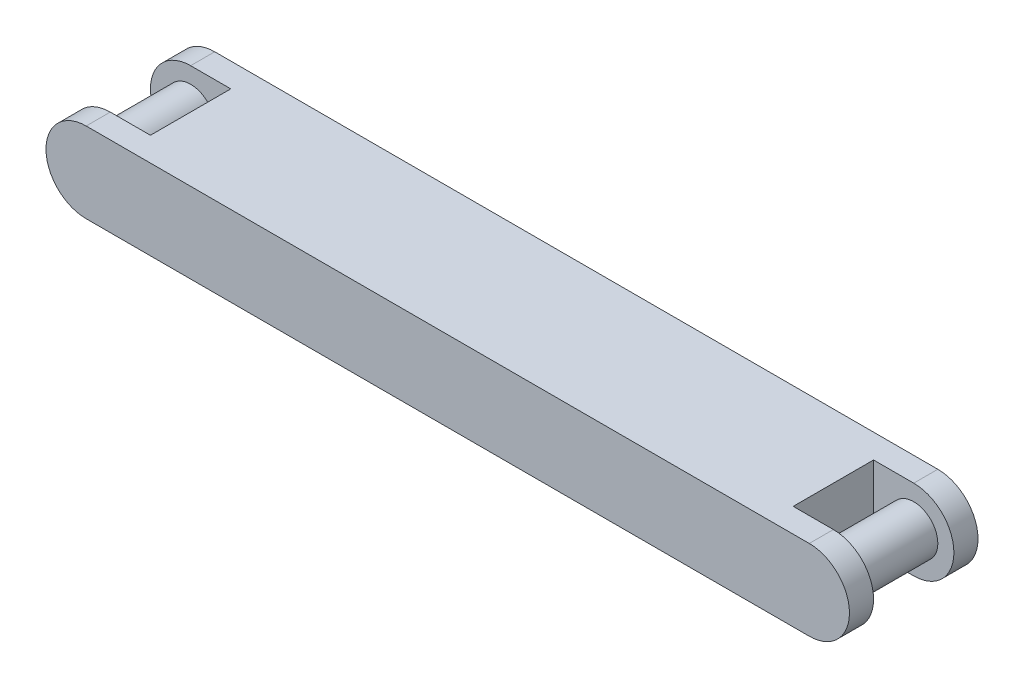
SolidWorks part; units mm, degrees
ref_plane "Front Plane" through (0, 0, 0) normal (0, 0, 1) x (1, 0, 0)
ref_plane "Top Plane" through (0, 0, 0) normal (0, 1, 0) x (1, 0, 0)
ref_plane "Right Plane" through (0, 0, 0) normal (1, 0, 0) x (0, 0, -1)
sketch "Sketch1" plane through (0, 0, 0) normal (0, 0, 1) x (1, 0, 0)
  line L0 (-142.875, 15.875) -> (-127, 15.875)
  line L1 (-127, -15.875) -> (127, -15.875)
  line L2 (-127, -15.875) -> (-127, 15.875)
  line L3 (-127, 15.875) -> (127, 15.875)
  line L4 (127, -15.875) -> (127, 15.875)
  line L5 (-127, -15.875) -> (127, 15.875) construction
  line L6 (-127, 15.875) -> (127, -15.875) construction
  line L7 (-142.875, -15.875) -> (-127, -15.875)
  line L8 (0, 15.875) -> (0, -15.875) construction
  line L9 (142.875, -15.875) -> (127, -15.875)
  line L10 (142.875, 15.875) -> (127, 15.875)
  circle A0 centre (-142.875, 0) radius 9.525
  circle A1 centre (-142.875, 0) radius 15.875
  circle A2 centre (142.875, 0) radius 9.525
  circle A3 centre (142.875, 0) radius 15.875
  point P0 (0, 0)
  dimension "D1" = 31.75
  dimension "D2" = 19.05
  dimension "D3" = 254
extrude "Boss-Extrude1" add sketch "Sketch1" along normal blind 25.4 and the other way blind 25.4 contours L1 L4 L3 L2 | A0 | A2 region at (0, 0, 0)
extrude "Boss-Extrude2" add sketch "Sketch1<4>" against normal blind 9.525 from surface contours A1 L2 L0 | A1 A0 | A1 L7 L2 | L4 A3 L10 | A3 A2 | L9 A3 L4 region at (-130.546, 12.329, 0) region at (-131.9672, 10.9078, 0) region at (-130.546, -12.329, 0) region at (130.546, 12.329, 0) region at (130.546, -12.329, 0) region at (131.9672, 10.9078, 0) starting at face at (0, 0, 25.4)
sketch "Sketch1<4>" plane through (0, 0, 0) normal (0, 0, 1) x (1, 0, 0) same geometry as "Sketch1"
extrude "Boss-Extrude3" add sketch "Sketch1<5>" along normal blind 9.525 from surface contours A1 A0 | A1 L2 L0 | A1 L7 L2 | L4 A3 L10 | A3 A2 | L9 A3 L4 region at (-130.546, 12.329, 0) region at (-131.9672, 10.9078, 0) region at (-130.546, -12.329, 0) region at (130.546, 12.329, 0) region at (130.546, -12.329, 0) region at (131.9672, 10.9078, 0) starting at face at (0, 0, -25.4)
sketch "Sketch1<5>" plane through (0, 0, 0) normal (0, 0, 1) x (1, 0, 0) same geometry as "Sketch1"
